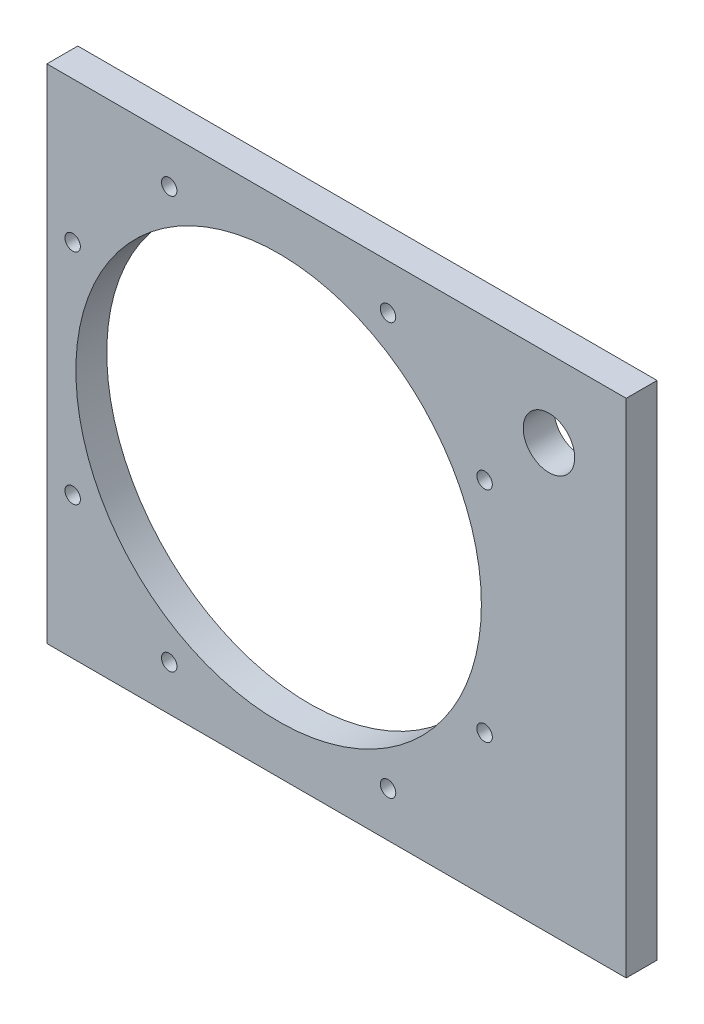
SolidWorks part; units mm, degrees
ref_plane "前视基准面" through (0, 0, 0) normal (0, 0, 1) x (1, 0, 0)
ref_plane "上视基准面" through (0, 0, 0) normal (0, 1, 0) x (1, 0, 0)
ref_plane "右视基准面" through (0, 0, 0) normal (1, 0, 0) x (0, 0, -1)
other "Configuration Table"
sketch "草图1" plane through (0, 0, 0) normal (0, 0, 1) x (1, 0, 0)
  line L0 (-225, 0) -> (0, 0) construction
  line L1 (-225, 195) -> (225, 195)
  line L2 (-225, 195) -> (-225, -195)
  line L3 (-225, -195) -> (225, -195)
  line L4 (225, 195) -> (225, -195)
  line L5 (-225, 195) -> (225, -195) construction
  line L6 (-225, -195) -> (225, 195) construction
  line L7 (0, 0) -> (0, 195) construction
  line L8 (-45, 0) -> (-45, 195) construction
  circle A0 centre (-45, 0) radius 157.5
  circle A3 centre (-205, 85) radius 6
  circle A4 centre (-205, -85) radius 6
  circle A5 centre (40, 160) radius 6
  circle A6 centre (-130, 160) radius 6
  circle A7 centre (115, -85) radius 6
  circle A8 centre (115, 85) radius 6
  circle A9 centre (-130, -160) radius 6
  circle A10 centre (40, -160) radius 6
  circle A11 centre (165, 135) radius 20
  point P0 (0, 0)
  point P31 (-45, 0)
  dimension "D3" = 315
  dimension "D5" = 12
  dimension "D11" = 40
  dimension "D1" = 450
  dimension "D2" = 390
  dimension "D4" = 180
  dimension "D6" = 4
  dimension "D7" = 170
  dimension "D8" = 320
  dimension "D9" = 60
  dimension "D10" = 60
extrude "凸台-拉伸1" add sketch "草图1" along normal blind 24
sketch "草图2" plane through (0, -195, 0) normal (0, 1, 0) x (1, 0, 0)
  line L0 (225, -24) -> (-225, -24) construction
  line L1 (-225, -24) -> (-225, 0) construction
  circle A0 centre (-155, -9.5) radius 4
  circle A1 centre (-25, -9.5) radius 4
  dimension "D1" = 8
  dimension "D4" = 130
  dimension "D2" = 14.5
  dimension "D3" = 70
extrude "切除-拉伸1" cut sketch "草图2" along normal blind 20
